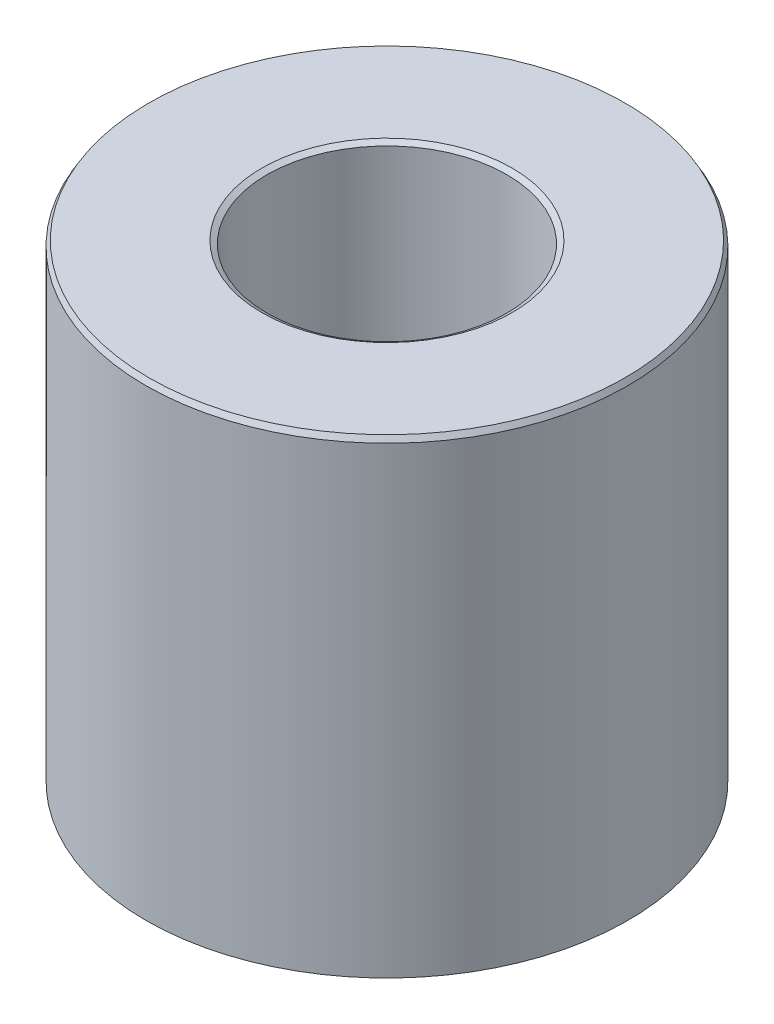
SolidWorks part; units mm, degrees
ref_plane "Front Plane" through (0, 0, 0) normal (0, 0, 1) x (1, 0, 0)
ref_plane "Top Plane" through (0, 0, 0) normal (0, 1, 0) x (1, 0, 0)
ref_plane "Right Plane" through (0, 0, 0) normal (1, 0, 0) x (0, 0, -1)
sketch "Sketch1" plane through (0, 0, 0) normal (0, 1, 0) x (1, 0, 0)
  circle A0 centre (0, 0) radius 60
  dimension "SLEEVE_OD" = 120
extrude "Boss-Extrude1" add sketch "Sketch1" along normal blind 117.3265
sketch "Sketch2" plane through (0, 0, 0) normal (0, 1, 0) x (1, 0, 0)
  circle A0 centre (0, 0) radius 29.8489
  dimension "BORE_D" = 59.6977
extrude "Cut-Extrude1" cut sketch "Sketch2" along normal through all
chamfer "Chamfer1" distance 1.3108 angle 30 4 edges at (0, 117.3265, 29.8489) (0, 0, 29.8489) (0, 0, 60) (0, 117.3265, 60) first distance on face at (0, 117.3265, 29.8489) first distance on face at (0, 0, 29.8489) first distance on face at (0, 117.3265, 60)
